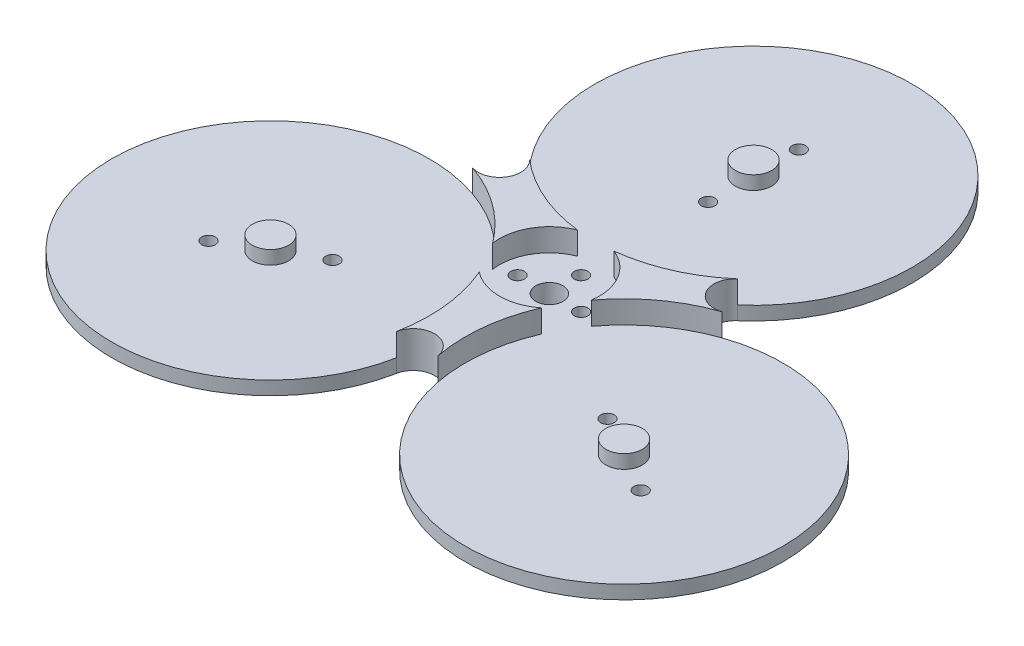
SolidWorks part; units mm, degrees
ref_plane "前视基准面" through (0, 0, 0) normal (0, 0, 1) x (1, 0, 0)
ref_plane "上视基准面" through (0, 0, 0) normal (0, 1, 0) x (1, 0, 0)
ref_plane "右视基准面" through (0, 0, 0) normal (1, 0, 0) x (0, 0, -1)
other "Configuration Table"
sketch "草图1" plane through (0, 0, 0) normal (0, 1, 0) x (1, 0, 0)
  line L0 (0, 0) -> (0, 92.6441) construction
  line L1 (0, 0) -> (108.3188, 62.5379) construction
  circle A0 centre (0, 0) radius 80 construction
  circle A1 centre (0, 0) radius 45 construction
  circle A5 centre (0, 45) radius 35 construction
  circle A6 centre (0, 0) radius 3
  circle A7 centre (0, 0) radius 7 construction
  circle A8 centre (0, 7) radius 1.5
  circle A9 centre (0, 0) radius 10 construction
  circle A10 centre (38.9711, -22.5) radius 35 construction
  circle A11 centre (-38.9711, -22.5) radius 35 construction
  circle A12 centre (7, 0) radius 1.5
  circle A13 centre (0, -7) radius 1.5
  circle A14 centre (-7, 0) radius 1.5
  arc A15 (0, 80) -> (22.9129, 18.5425) centre (0, 45) cw
  arc A16 (22.9129, 18.5425) -> (27.5147, 10.5719) centre (25.9808, 15) ccw
  arc A17 (69.282, -40) -> (27.5147, 10.5719) centre (38.9711, -22.5) ccw
  arc A18 (4.6018, -29.1144) -> (-4.6018, -29.1144) centre (0, -30) ccw
  arc A19 (69.282, -40) -> (4.6018, -29.1144) centre (38.9711, -22.5) cw
  arc A20 (-69.282, -40) -> (-4.6018, -29.1144) centre (-38.9711, -22.5) ccw
  arc A21 (-27.5147, 10.5719) -> (-22.9129, 18.5425) centre (-25.9808, 15) ccw
  arc A22 (-69.282, -40) -> (-27.5147, 10.5719) centre (-38.9711, -22.5) cw
  arc A23 (0, 80) -> (-22.9129, 18.5425) centre (0, 45) ccw
  circle A24 centre (0, 55) radius 1.5
  circle A25 centre (0, 35) radius 1.5
  circle A26 centre (47.6314, -27.5) radius 1.5
  circle A27 centre (30.3109, -17.5) radius 1.5
  circle A28 centre (-47.6314, -27.5) radius 1.5
  circle A29 centre (-30.3109, -17.5) radius 1.5
  point P13 (0, 0)
  point P19 (0, 0)
  point P26 (0, 0)
  point P48 (0, 0)
  point P58 (0, 0)
  dimension "D1" = 160
  dimension "D2" = 3
  dimension "D3" = 14
  dimension "D5" = 70
  dimension "D4" = 6
  dimension "D6" = 3
  dimension "D7" = 20
  dimension "D12" = 3
  dimension "D9" = 60
  dimension "D10" = 3
  dimension "D11" = 30
  dimension "D13" = 10
  dimension "D14" = 10
  dimension "D8" = 4
  dimension "D15" = 3
extrude "凸台-拉伸1" add sketch "草图1" along normal blind 8
sketch "草图2" plane through (0, 0, 0) normal (0, -1, 0) x (1, 0, 0)
  circle A0 centre (0, 0) radius 10
  circle A1 centre (-7, 0) radius 1.5 construction
  circle A2 centre (0, -7) radius 1.5 construction
  circle A3 centre (7, 0) radius 1.5 construction
  circle A4 centre (0, 7) radius 1.5 construction
  circle A5 centre (0, 0) radius 3 construction
  circle A6 centre (-7, 0) radius 1.5
  circle A7 centre (0, -7) radius 1.5
  circle A8 centre (7, 0) radius 1.5
  circle A9 centre (0, 7) radius 1.5
  circle A10 centre (0, 0) radius 3
  dimension "D1" = 20
extrude "凸台-拉伸2" add sketch "草图2" along normal blind 8
sketch "草图3" plane through (0, 8, 0) normal (0, 1, 0) x (1, 0, 0)
  circle A0 centre (0, 45) radius 35
  arc A1 (22.9129, 18.5425) -> (-22.9129, 18.5425) centre (0, 45) ccw construction
  circle A2 centre (38.9711, -22.5) radius 35
  circle A3 centre (-38.9711, -22.5) radius 35
  circle A4 centre (0, 0) radius 11
  circle A5 centre (0, 45) radius 4
  circle A6 centre (38.9711, -22.5) radius 4
  circle A7 centre (-38.9711, -22.5) radius 4
  point P12 (0, 0)
  point P21 (0, 0)
  arc M4 (22.9129, 18.5425) -> (-22.9129, 18.5425) centre (0, 45) ccw
  arc M6 (-27.5147, 10.5719) -> (-4.6018, -29.1144) centre (-38.9711, -22.5) ccw
  arc M8 (4.6018, -29.1144) -> (27.5147, 10.5719) centre (38.9711, -22.5) ccw
  dimension "D2" = 8
  dimension "D3" = 22
  dimension "D1" = 3
  dimension "D4" = 3
extrude "切除-拉伸2" cut sketch "草图3" against normal blind 5 contours A0 M4 | A2 M8 | A3 M6 | A4 region at (30.9362, 8, -30.8668) region at (-10.3836, 8, 5.995) region at (18.8638, 8, -4.9295)
chamfer "倒角1" distance 3 angle 45 1 edges at (0, 0, 10)
extrude "切除-拉伸3" cut sketch "草图3<4>" against normal blind 2 contours A7 | A6 | A5 region at (0, 8, -45) region at (38.9711, 8, 22.5) region at (-38.9711, 8, 22.5)
sketch "草图3<4>" plane through (0, 8, 0) normal (0, 1, 0) x (1, 0, 0) same geometry as "草图3"
